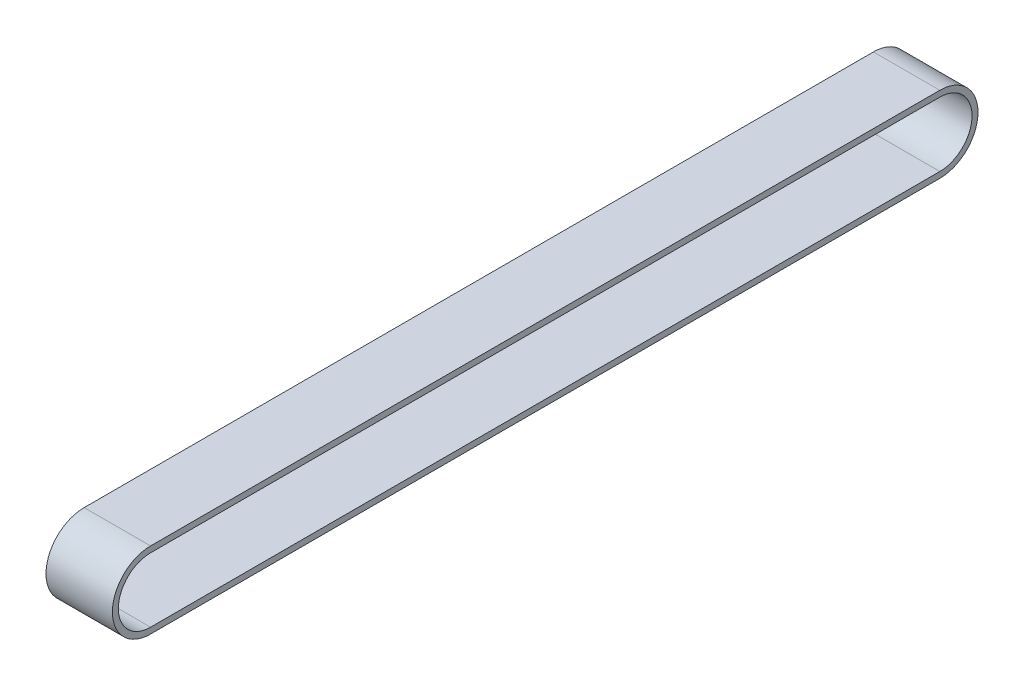
SolidWorks part; units mm, degrees
material "PUR"
ref_plane "Front" through (0, 0, 0) normal (0, 0, 1) x (1, 0, 0)
ref_plane "Top" through (0, 0, 0) normal (0, 1, 0) x (1, 0, 0)
ref_plane "Right" through (0, 0, 0) normal (1, 0, 0) x (0, 0, -1)
sketch "Sketch1" plane through (0, 0, 0) normal (1, 0, 0) x (0, 0, -1)
  line L0 (-150.9824, 0) -> (150.9824, 0) construction
  line L1 (-150.9824, 14.605) -> (150.9824, 14.605)
  line L2 (-150.9824, -14.605) -> (150.9824, -14.605)
  line L3 (-150.9824, 0) -> (150.9824, 0) construction
  line L4 (-150.9824, 12.319) -> (150.9824, 12.319)
  line L5 (-150.9824, -12.319) -> (150.9824, -12.319)
  arc A0 (-150.9824, 14.605) -> (-150.9824, -14.605) centre (-150.9824, 0) ccw
  arc A1 (150.9824, -14.605) -> (150.9824, 14.605) centre (150.9824, 0) ccw
  arc A2 (-150.9824, 12.319) -> (-150.9824, -12.319) centre (-150.9824, 0) ccw
  arc A3 (150.9824, -12.319) -> (150.9824, 12.319) centre (150.9824, 0) ccw
  point P2 (0, 0)
  point P9 (0, 0)
  dimension "D2" = 24.638
  dimension "D1" = 2.286
  dimension "D3" = 301.9648
extrude "Boss-Extrude1" add sketch "Sketch1" along normal mid plane 25.4
